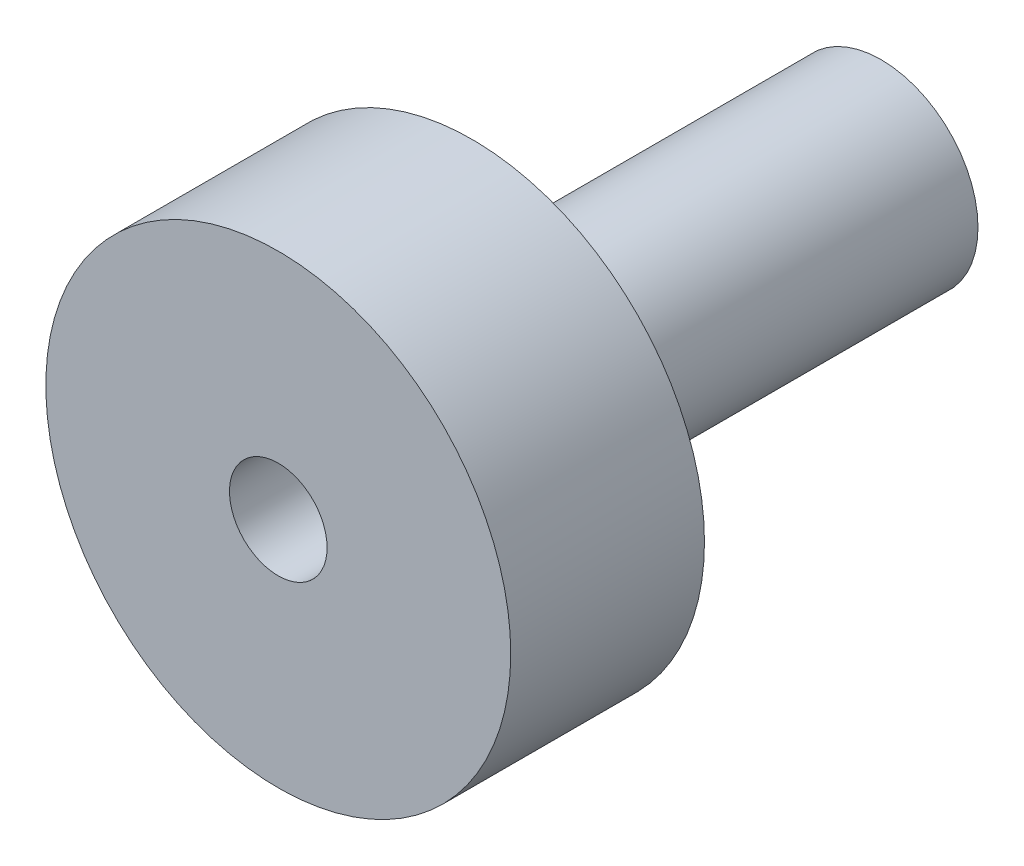
SolidWorks part; units mm, degrees
material "Delrin 2700 NC010, Low Viscosity Acetal Copolymer (SS)"
ref_plane "Front Plane" through (0, 0, 0) normal (0, 0, 1) x (1, 0, 0)
ref_plane "Top Plane" through (0, 0, 0) normal (0, 1, 0) x (1, 0, 0)
ref_plane "Right Plane" through (0, 0, 0) normal (1, 0, 0) x (0, 0, -1)
sketch "Sketch1" plane through (0, 0, 0) normal (0, 0, 1) x (1, 0, 0)
  circle A0 centre (0, 0) radius 9.525
  circle A1 centre (0, 0) radius 2
  dimension "D1" = 19.05
  dimension "D2" = 4
extrude "Boss-Extrude1" add sketch "Sketch1" along normal blind 7.9375
sketch "Sketch2" plane through (0, 0, 0) normal (0, 0, -1) x (-1, 0, 0)
  circle A0 centre (0, 0) radius 3.9688
  dimension "D1" = 7.9375
extrude "Boss-Extrude2" add sketch "Sketch2" along normal blind 16.764
sketch "Sketch3" plane through (0, 0, 7.9375) normal (0, 0, 1) x (1, 0, 0)
  circle A0 centre (0, 0) radius 2
extrude "Cut-Extrude1" cut sketch "Sketch3" against normal through all
